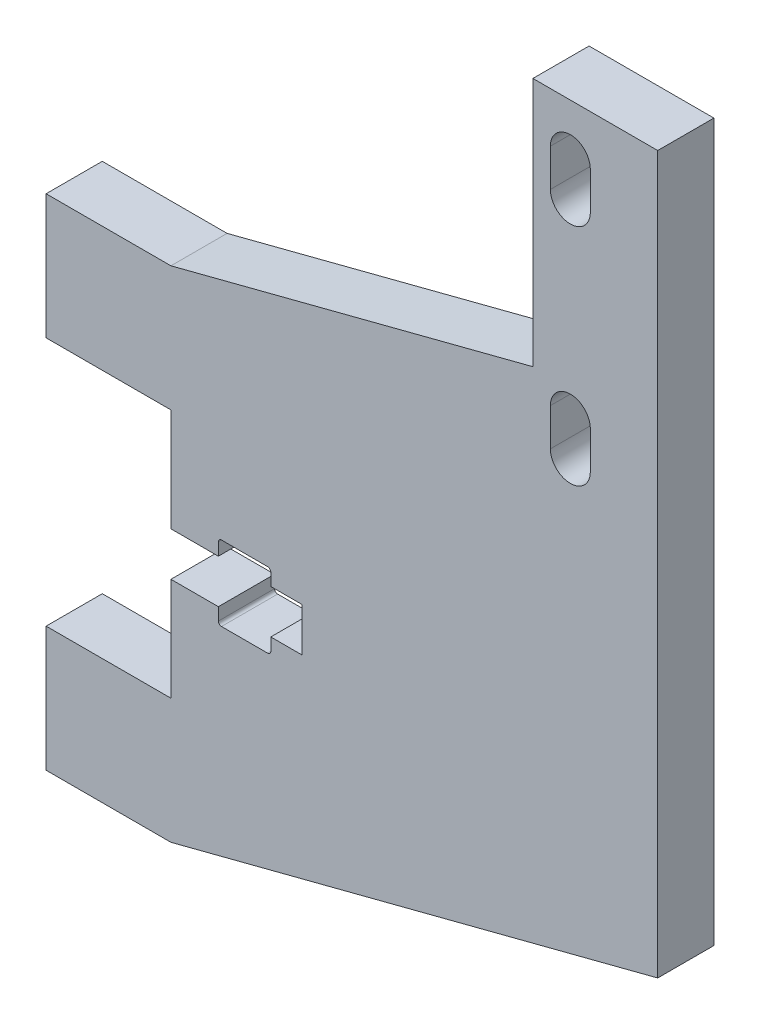
SolidWorks part; units mm, degrees
ref_plane "Front Plane" through (0, 0, 0) normal (0, 0, 1) x (1, 0, 0)
ref_plane "Top Plane" through (0, 0, 0) normal (0, 1, 0) x (1, 0, 0)
ref_plane "Right Plane" through (0, 0, 0) normal (1, 0, 0) x (0, 0, -1)
sketch "Sketch1" plane through (0, 0, 0) normal (0, 0, 1) x (1, 0, 0)
  line L0 (29, 2.5) -> (0, -5)
  line L1 (0, -5) -> (-10, -5)
  line L2 (-10, -5) -> (-10, -15)
  line L3 (-10, -15) -> (0, -15)
  line L4 (0, -15) -> (0, -35)
  line L5 (0, -35) -> (-10, -35)
  line L6 (-10, -35) -> (-10, -45)
  line L7 (-10, -45) -> (0, -45)
  line L10 (0, -45) -> (39, -34.9138)
  line L11 (39, -34.9138) -> (39, 22.5)
  line L12 (39, 22.5) -> (29, 22.5)
  line L13 (29, 22.5) -> (29, 2.5)
  line L15 (0, -5) -> (0, -45) construction
  line L16 (-10, -10) -> (0, -10) construction
  line L17 (-10, -40) -> (0, -40) construction
  line L18 (-10, -15) -> (-10, -35) construction
  line L19 (-10, -25) -> (0, -25) construction
  dimension "D2" = 10
  dimension "D3" = 10
  dimension "D4" = 10
  dimension "D5" = 15
  dimension "D8" = 10
  dimension "D9" = 20
  dimension "D10" = 29
  dimension "D6" = 67.5
extrude "Boss-Extrude1" add sketch "Sketch1" along normal blind 4.5
sketch "Sketch2" plane through (0, 0, 4.5) normal (0, 0, 1) x (1, 0, 0)
  line L0 (0, -25) -> (39, -25) construction
  line L1 (0, -15) -> (0, -35) construction
  line L3 (10.5, -26.75) -> (10.5, -23.25) construction
  line L4 (10.5, -23.25) -> (0, -23.25) construction
  line L5 (0, -26.75) -> (0, -23.25)
  line L6 (0, -23.25) -> (3.8, -23.25)
  line L7 (3.8, -23.25) -> (3.8, -22.25)
  line L8 (4.05, -22) -> (7.75, -22)
  line L9 (8, -22.25) -> (8, -23.25)
  line L10 (8, -23.25) -> (10.5, -23.25)
  line L11 (10.5, -23.25) -> (10.5, -26.75)
  line L12 (10.5, -26.75) -> (0, -26.75) construction
  line L13 (8, -26.75) -> (10.5, -26.75)
  line L14 (8, -27.75) -> (8, -26.75)
  line L15 (4.05, -28) -> (7.75, -28)
  line L16 (3.8, -26.75) -> (3.8, -27.75)
  line L17 (0, -26.75) -> (3.8, -26.75)
  line L18 (39, -34.9138) -> (39, 22.5) construction
  arc A0 (7.75, -22) -> (8, -22.25) centre (7.75, -22.25) cw
  arc A1 (3.8, -22.25) -> (4.05, -22) centre (4.05, -22.25) cw
  arc A2 (3.8, -27.75) -> (4.05, -28) centre (4.05, -27.75) ccw
  arc A3 (7.75, -28) -> (8, -27.75) centre (7.75, -27.75) ccw
  point P15 (8, -22)
  point P18 (3.8, -22)
  point P27 (10.5, -25)
  point P29 (3.8, -28)
  point P30 (8, -28)
  dimension "D6" = 0.25
  dimension "D1" = 10.5
  dimension "D2" = 1.75
  dimension "D3" = 8
  dimension "D4" = 4.2
  dimension "D5" = 3
  dimension "D7" = 0
extrude "screw-cutout" cut sketch "Sketch2" against normal through all
sketch "Sketch3" plane through (0, 0, 4.5) normal (0, 0, 1) x (1, 0, 0)
  line L0 (32, 55) -> (32, -45) construction
  line L1 (39, 22.5) -> (29, 22.5) construction
  line L2 (32, 18.5) -> (32, 15.5) construction
  line L3 (29, 22.5) -> (29, 2.5) construction
  line L4 (33.6, 18.5) -> (33.6, 15.5)
  line L5 (-10, -45) -> (0, -45) construction
  line L6 (30.4, 18.5) -> (30.4, 15.5)
  line L7 (32, 0.5) -> (32, -2.5) construction
  line L8 (33.6, 0.5) -> (33.6, -2.5)
  line L9 (30.4, 0.5) -> (30.4, -2.5)
  arc A0 (33.6, 0.5) -> (30.4, 0.5) centre (32, 0.5) ccw
  arc A2 (33.6, 18.5) -> (30.4, 18.5) centre (32, 18.5) ccw
  arc A3 (30.4, 15.5) -> (33.6, 15.5) centre (32, 15.5) ccw
  arc A4 (30.4, -2.5) -> (33.6, -2.5) centre (32, -2.5) ccw
  point P8 (32, 17)
  point P14 (32, -1)
  dimension "D7" = 0
  dimension "D8" = 1.6
  dimension "D1" = 1.6
  dimension "D2" = 18
  dimension "D3" = 4
  dimension "D6" = 3
  dimension "D9" = 3
extrude "Cut-Extrude2" cut sketch "Sketch3" against normal through all
sketch "Sketch4" plane through (0, 0, 4.5) normal (0, 0, 1) x (1, 0, 0)
  line L0 (32, 0.5) -> (32, 18.5) construction
  line L1 (32, 9.5) -> (29, 9.5) construction
  line L2 (29, 22.5) -> (29, 2.5) construction
  line L4 (30, 13.5) -> (28, 13.5)
  line L5 (30, 13.5) -> (30, 5.5)
  line L6 (30, 5.5) -> (28, 5.5)
  line L7 (28, 13.5) -> (28, 5.5)
  line L8 (30, 13.5) -> (28, 5.5) construction
  line L9 (30, 5.5) -> (28, 13.5) construction
  arc A2 (33.6, 0.5) -> (30.4, 0.5) centre (32, 0.5) ccw construction
  arc A4 (33.6, 18.5) -> (30.4, 18.5) centre (32, 18.5) ccw construction
  point P11 (29, 9.5)
  dimension "D1" = 8
  dimension "D2" = 2
  dimension "D3" = 3
  dimension "D4" = 0
  dimension "D5" = 0
equation "\"X-ROD-SPACING\"=45"
equation "\"Y-ROD-SPACING\"=75"
equation "\"Z-ROD-SPACING\"=17.5"
equation "\"Y-BED-OFFSET\"=2"
equation "\"Y-BED-ROD-INSET\"=3.5"
equation "\"T-SLOT-NUT-FILLET-RADIUS\"=0.25"
equation "\"T-SLOT-SCREW-SHAFT-RADIUS\"=1.75"
equation "\"T-SLOT-SCREW-SHAFT-CUTOUT-LENGTH\"=10.5"
equation "\"T-SLOT-NUT-DEPTH\"=4.2"
equation "\"T-SLOT-NUT-WIDTH\"=3"
equation "\"T-SLOT-NUT-END-DISTANCE\"=8"
equation "\"ACRYLIC-THICKNESS\"=10"
equation "\"ACRYLIC-THICKNESS2\"=4.5"
equation "\"ACRYLIC-TAB-CUTOUT-SIZE\"=\"ACRYLIC-THICKNESS\"+\"ACRYLIC-TAB-TOLERANCE\"*2"
equation "\"ACRYLIC-TAB-WIDTH\"=\"ACRYLIC-THICKNESS\""
equation "\"ACRYLIC-M3-HOLE\"=3.2"
equation "\"SMOOTHROD-CAP-SCREW-DISTANCE\"=20"
equation "\"FRAME-WIDTH-INNER\"=370"
equation "\"NEMA17-HOLE-SPACING\"=31"
equation "\"NEMA17-CENTRAL-CUTOUT\"=22.5"
equation "\"Z-BRACKET-REACH\"=55"
equation "\"Z-ROD-INSET\"=16"
equation "\"TOP-BRACKET-SPACING\"=40"
equation "\"SMOOTHROD-X-LENGTH\"=350"
equation "\"SMOOTHROD-Y-LENGTH\"=350"
equation "\"SMOOTHROD-Z-LENGTH\"=350"
equation "\"SMOOTHROD-TIGHTENING-HEADROOM\"=1"
equation "\"LEADSCREW-Z-LENGTH\"=300"
equation "\"SCREW-LENGTH-FRAME\"=\"ACRYLIC-THICKNESS\" + 10"
equation "\"SCREW-HEAD-RADIUS\"=6"
equation "\"PRINTED-X-SMOOTHROD-DIAMETER\"=8.2"
equation "\"PRINTED-X-SMOOTHROD-CUTOUT\"=10"
equation "\"PRINTED-X-BASE-HEIGHT\"=10"
equation "\"PRINTED-LM8UU-CUTOUT-SIZE\"=16"
equation "\"PRINTED-LM8UU-CUTOUT-LENGTH\"=24.5"
equation "\"PRINTED-X-IDLER-HEIGHT\"=16"
equation "\"PSU-MOUNTING-WIDTH\"=95"
equation "\"PSU-MOUNTING-HEIGHT\"=177"
equation "\"Y-BELT-TO-ROD-DISTANCE\"=20"
equation "\"SPOOL-HOLDER-ROD-SPACING\"=150"
equation "\"D1@Sketch1\"=\"ACRYLIC-TAB-WIDTH\""
equation "\"D2@Sketch1\"=\"ACRYLIC-TAB-WIDTH\""
equation "\"D3@Sketch1\"=\"ACRYLIC-THICKNESS\""
equation "\"D4@Sketch1\"=\"ACRYLIC-THICKNESS\""
equation "\"D1@Boss-Extrude1\"=\"ACRYLIC-THICKNESS2\""
equation "\"D1@Sketch2\"=\"T-SLOT-SCREW-SHAFT-CUTOUT-LENGTH\""
equation "\"D2@Sketch2\"=\"T-SLOT-SCREW-SHAFT-RADIUS\""
equation "\"D3@Sketch2\"=\"T-SLOT-NUT-END-DISTANCE\""
equation "\"D4@Sketch2\"=\"T-SLOT-NUT-DEPTH\""
equation "\"D5@Sketch2\"=\"T-SLOT-NUT-WIDTH\""
equation "\"D6@Sketch2\"=\"T-SLOT-NUT-FILLET-RADIUS\""
equation "\"D1@Sketch3\"=\"ACRYLIC-M3-HOLE\"/2"
equation "\"D8@Sketch3\"=\"ACRYLIC-M3-HOLE\"/2"
